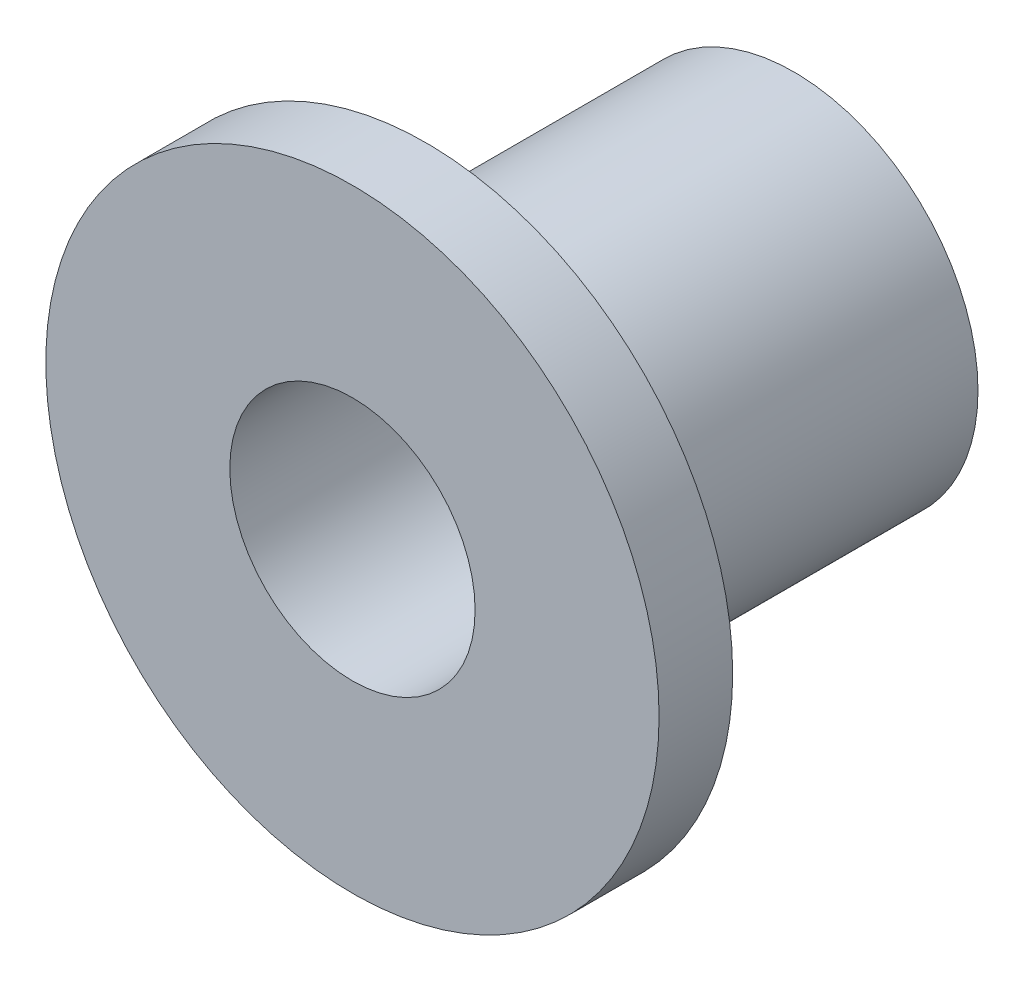
SolidWorks part; units mm, degrees
material "Plain Carbon Steel"
ref_plane "Front Plane" through (0, 0, 0) normal (0, 0, 1) x (1, 0, 0)
ref_plane "Top Plane" through (0, 0, 0) normal (0, 1, 0) x (1, 0, 0)
ref_plane "Right Plane" through (0, 0, 0) normal (1, 0, 0) x (0, 0, -1)
sketch "Sketch1" plane through (0, 0, 0) normal (0, 0, 1) x (1, 0, 0)
  circle A0 centre (0, 0) radius 5
  circle A1 centre (0, 0) radius 7.5
  circle A2 centre (0, 0) radius 12.5
  dimension "D1" = 25
  dimension "D2" = 15
  dimension "D3" = 10
extrude "Boss-Extrude1" add sketch "Sketch1" along normal blind 3 contours A2 A1 | A1 A0 region at (-7.2879, 0, 0) region at (-12.1464, 0, 0)
extrude "Boss-Extrude2" add sketch "Sketch1<3>" against normal blind 15 contours A1 A0 region at (-7.2879, 0, 0)
sketch "Sketch1<3>" plane through (0, 0, 0) normal (0, 0, 1) x (1, 0, 0) same geometry as "Sketch1"
